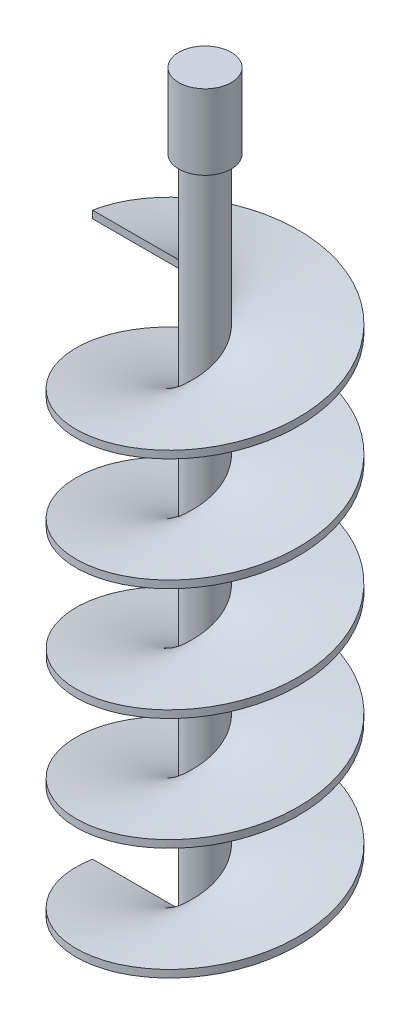
SolidWorks part; units mm, degrees
ref_plane "Front Plane" through (0, 0, 0) normal (0, 0, 1) x (1, 0, 0)
ref_plane "Top Plane" through (0, 0, 0) normal (0, 1, 0) x (1, 0, 0)
ref_plane "Right Plane" through (0, 0, 0) normal (1, 0, 0) x (0, 0, -1)
sketch "Sketch1" plane through (0, 0, 0) normal (0, 1, 0) x (1, 0, 0)
  circle A0 centre (0, 0) radius 5
  dimension "D1" = 10
extrude "Boss-Extrude1" add sketch "Sketch1" along normal blind 200
sketch "Sketch3" plane through (0, 0, 0) normal (0, -1, 0) x (1, 0, 0)
  circle A0 centre (0, 0) radius 5 construction
  circle A1 centre (0, 0) radius 5
curve "Helix/Spiral1" pitch 30 height 150 radius 5 centre (0, 0, 0) axis (0, 1, 0) start towards (0, 0, -1)
sketch "Sketch4" plane through (0, 0, 0) normal (0, 0, 1) x (1, 0, 0)
  line L0 (-5, 0) -> (-30, 0)
  line L1 (-30, 0) -> (-30, 2)
  line L2 (-30, 2) -> (-4.5678, 2)
  line L3 (-4.5678, 2) -> (-4.5678, 0)
  line L4 (-5, 0) -> (5, 0) construction
  line L5 (-4.5678, 0) -> (-5, 0)
  spline S0 degree 3 poles (-5, 0) (-5, 0.6229) (-4.7397, 1.876) (-3.6276, 3.7497) (-1.9632, 5.6251) (0, 7.5) (1.9632, 9.375) (3.6276, 11.25) (4.7397, 13.125) (5.1302, 15) (4.7397, 16.875) (3.6276, 18.75) (1.4084, 21.25) (-1.4084, 23.75) (-3.6276, 26.25) (-4.7397, 28.125) (-5.1302, 30) (-4.7397, 31.875) (-3.6276, 33.75) (-1.4084, 36.25) (1.4084, 38.75) (3.6276, 41.25) (4.7397, 43.125) (5.1302, 45) (4.7397, 46.875) (3.6276, 48.75) (1.4084, 51.25) (-1.4084, 53.75) (-3.6276, 56.25) (-4.7397, 58.125) (-5.1302, 60) (-4.7397, 61.875) (-3.6276, 63.75) (-1.4084, 66.25) (1.4084, 68.75) (3.6276, 71.25) (4.7397, 73.125) (5.1302, 75) (4.7397, 76.875) (3.6276, 78.75) (1.4084, 81.25) (-1.4084, 83.75) (-3.6276, 86.25) (-4.7397, 88.125) (-5.1302, 90) (-4.7397, 91.875) (-3.6276, 93.75) (-1.4084, 96.25) (1.4084, 98.75) (3.6276, 101.25) (4.7397, 103.125) (5.1302, 105) (4.7397, 106.875) (3.6276, 108.75) (1.4084, 111.25) (-1.4084, 113.75) (-3.6276, 116.25) (-4.7397, 118.125) (-5.1302, 120) (-4.7397, 121.875) (-3.6276, 123.75) (-1.4084, 126.25) (1.4084, 128.75) (3.6276, 131.25) (4.7397, 133.125) (5.1302, 135) (4.7397, 136.875) (3.6276, 138.75) (1.9632, 140.625) (0, 142.5) (-1.9632, 144.3749) (-3.6276, 146.2503) (-4.7397, 148.124) (-5, 149.3771) (-5, 150) knots 0 0 0 0 0.0125 0.025 0.0375 0.05 0.0625 0.075 0.0875 0.1 0.1125 0.125 0.1375 0.1625 0.175 0.1875 0.2 0.2125 0.225 0.2375 0.2625 0.275 0.2875 0.3 0.3125 0.325 0.3375 0.3625 0.375 0.3875 0.4 0.4125 0.425 0.4375 0.4625 0.475 0.4875 0.5 0.5125 0.525 0.5375 0.5625 0.575 0.5875 0.6 0.6125 0.625 0.6375 0.6625 0.675 0.6875 0.7 0.7125 0.725 0.7375 0.7625 0.775 0.7875 0.8 0.8125 0.825 0.8375 0.8625 0.875 0.8875 0.9 0.9125 0.925 0.9375 0.95 0.9625 0.975 0.9875 1 1 1 1 construction
  dimension "D1" = 30
  dimension "D2" = 2
sweep "Sweep1" add profiles "Sketch4" path "Helix/Spiral1"
sketch "Sketch5" plane through (0, 200, 0) normal (0, 1, 0) x (1, 0, 0)
  circle A0 centre (0, 0) radius 7
  dimension "D1" = 14
extrude "Boss-Extrude2" add sketch "Sketch5" against normal blind 20
